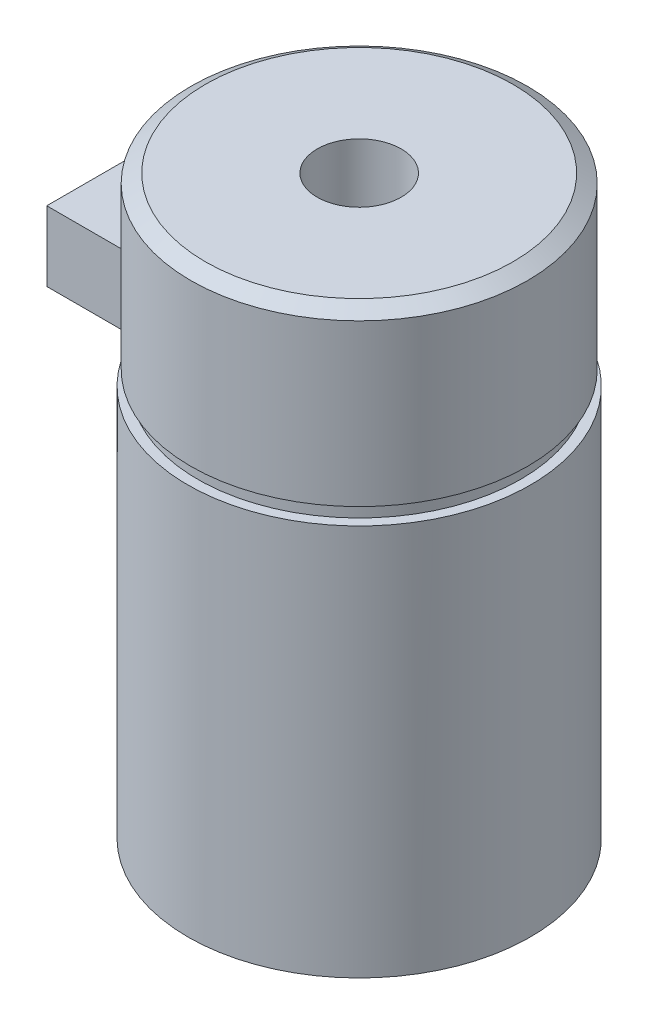
SolidWorks part; units mm, degrees
ref_plane "前视基准面" through (0, 0, 0) normal (0, 0, 1) x (1, 0, 0)
ref_plane "上视基准面" through (0, 0, 0) normal (0, 1, 0) x (1, 0, 0)
ref_plane "右视基准面" through (0, 0, 0) normal (1, 0, 0) x (0, 0, -1)
sketch "草图3" plane through (0, 0, 0) normal (0, 1, 0) x (1, 0, 0)
  circle A0 centre (0, 0) radius 12.25
  dimension "D1" = 24.5
extrude "凸台-拉伸1" add sketch "草图3" along normal blind 28
sketch "草图4" plane through (0, 0, 0) normal (0, 0, 1) x (1, 0, 0)
  line L0 (-11.5507, 28) -> (0, 28)
  line L1 (-12.0399, 29.049) -> (-12.0399, 40.557)
  line L2 (0, 28) -> (0, 41.2)
  line L3 (-11, 41.2) -> (0, 41.2)
  line L4 (12.25, 28) -> (-12.25, 28) construction
  line L5 (-12.0399, 40.557) -> (-11, 41.2)
  line L11 (-12.0399, 29.049) -> (-11.5507, 29.049)
  line L14 (-11.5507, 29.049) -> (-11.5507, 28)
  dimension "D1" = 13.2
  dimension "D3" = 11
revolve "旋转1" add sketch "草图4" angle 360 about L2
sketch "草图6" plane through (0, 0, 0) normal (0, 0, 1) x (1, 0, 0)
  line L0 (-12.25, 0) -> (12.25, 0) construction
  line L1 (-8.9296, 32) -> (-18.348, 32)
  line L2 (-8.9296, 32) -> (-8.9296, 27)
  line L3 (-8.9296, 27) -> (-18.348, 27)
  line L4 (-18.348, 32) -> (-18.348, 27)
  dimension "D1" = 9.4184
  dimension "D2" = 5
  dimension "D3" = 27
extrude "凸台-拉伸4" add sketch "草图6" along normal blind 4 and the other way blind 4 contours L1 L4 L3 L2
sketch "草图10" plane through (0, 0, 0) normal (0, -1, 0) x (1, 0, 0)
  circle A0 centre (0, 0) radius 6.5
  dimension "D1" = 13
extrude "凸台-拉伸5" add sketch "草图10" along normal blind 2.5
sketch "草图11" plane through (0, -2.5, 0) normal (0, -1, 0) x (1, 0, 0)
  circle A0 centre (0, 0) radius 3
extrude "切除-拉伸1" cut sketch "草图11" against normal through all both and the other way through all
sketch "草图12" plane through (0, 0, 0) normal (0, -1, 0) x (1, 0, 0)
  circle A0 centre (0, 0) radius 11
  point P3 (-11, 0)
  point P4 (0, 11)
  point P5 (11, 0)
  point P6 (0, -11)
sketch "Sketch1" plane through (0, 0, 0) normal (0, -1, 0) x (1, 0, 0)
  circle A0 centre (9.5, 0) radius 1.5
  circle A1 centre (-4.75, -8.2272) radius 1.5
  circle A2 centre (-4.75, 8.2272) radius 1.5
  point P9 (0, 0)
  dimension "D1" = 3
  dimension "D2" = 9.5
  dimension "D3" = 3
extrude "Cut-Extrude1" cut sketch "Sketch1" against normal blind 10
